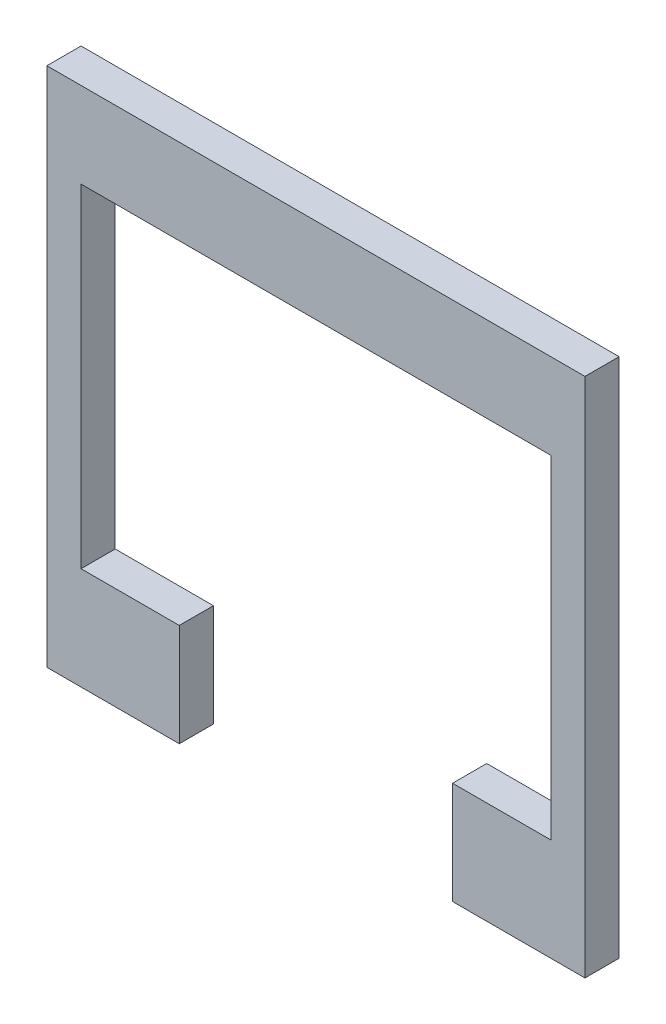
SolidWorks part; units mm, degrees
ref_plane "Front" through (0, 0, 0) normal (0, 0, 1) x (1, 0, 0)
ref_plane "Top" through (0, 0, 0) normal (0, 1, 0) x (1, 0, 0)
ref_plane "Right" through (0, 0, 0) normal (1, 0, 0) x (0, 0, -1)
sketch "Croquis1" plane through (0, 0, 0) normal (0, 0, 1) x (1, 0, 0)
  line L0 (0, 6.25) -> (0, -6.25) construction
  line L1 (-12.5, -6.25) -> (12.5, -6.25)
  line L2 (-12.5, -6.25) -> (-12.5, 6.25)
  line L3 (-12.5, 6.25) -> (12.5, 6.25)
  line L4 (12.5, -6.25) -> (12.5, 6.25)
  line L5 (-12.5, -6.25) -> (12.5, 6.25) construction
  line L6 (-12.5, 6.25) -> (12.5, -6.25) construction
  line L8 (-13.75, -11.25) -> (13.75, -11.25) construction
  line L9 (-13.75, -11.25) -> (-13.75, 8.25)
  line L10 (-13.75, 8.25) -> (13.75, 8.25)
  line L11 (13.75, -11.25) -> (13.75, 8.25)
  line L12 (-13.75, -11.25) -> (13.75, 8.25) construction
  line L13 (-13.75, 8.25) -> (13.75, -11.25) construction
  line L14 (-6, -16.25) -> (6, -16.25) construction
  line L15 (-6, -16.25) -> (-6, -6.25) construction
  line L16 (-6, -6.25) -> (6, -6.25) construction
  line L17 (6, -16.25) -> (6, -6.25) construction
  line L18 (-6, -16.25) -> (6, -6.25) construction
  line L19 (-6, -6.25) -> (6, -16.25) construction
  line L20 (-14.75, 12.25) -> (14.75, 12.25) construction
  line L21 (-14.75, 12.25) -> (-14.75, -16.25) construction
  line L22 (-14.75, -16.25) -> (14.75, -16.25) construction
  line L23 (14.75, 12.25) -> (14.75, -16.25) construction
  line L24 (-14.75, 12.25) -> (14.75, -16.25) construction
  line L25 (-14.75, -16.25) -> (14.75, 12.25) construction
  point P0 (0, 0)
  point P8 (0, 0)
  point P13 (0, -1.5)
  point P14 (0, -11.25)
  point P19 (0, -2)
  dimension "D1" = 12.5
  dimension "D2" = 25
  dimension "D3" = 2
  dimension "D4" = 27.5
  dimension "D5" = 19.5
  dimension "D6" = 12
  dimension "D7" = 5
  dimension "D8" = 1
  dimension "D9" = 4
sketch "Croquis4" plane through (0, 0, 0) normal (0, 0, 1) x (1, 0, 0)
  line L0 (-13.75, -11.25) -> (13.75, 8.25) construction
  line L1 (-13.75, -11.25) -> (-8, -11.25)
  line L2 (-13.75, -11.25) -> (-13.75, 8.25)
  line L3 (-13.75, 8.25) -> (13.75, 8.25)
  line L4 (13.75, -11.25) -> (13.75, 8.25)
  line L5 (-13.75, -11.25) -> (13.75, 8.25) construction
  line L6 (-13.75, 8.25) -> (13.75, -11.25) construction
  line L7 (0, 6.25) -> (0, -6.25) construction
  line L8 (-15.75, 13.25) -> (15.75, 13.25)
  line L9 (-15.75, 13.25) -> (-15.75, -17.25)
  line L10 (-15.75, -17.25) -> (-8, -17.25)
  line L11 (15.75, 13.25) -> (15.75, -17.25)
  line L12 (-15.75, 13.25) -> (15.75, -17.25) construction
  line L13 (-15.75, -17.25) -> (15.75, 13.25) construction
  line L14 (-14.75, 12.25) -> (14.75, 12.25) construction
  line L15 (-14.75, -16.25) -> (14.75, -16.25) construction
  line L16 (14.75, 12.25) -> (14.75, -16.25) construction
  line L17 (-8, -11.25) -> (-8, -17.25)
  line L18 (8, -11.25) -> (8, -17.25)
  line L19 (-6, -16.25) -> (-6, -6.25) construction
  line L20 (6, -16.25) -> (6, -6.25) construction
  line L21 (8, -17.25) -> (15.75, -17.25)
  line L22 (8, -11.25) -> (13.75, -11.25)
  point P0 (0, -1.5)
  point P8 (0, -2)
  dimension "D1" = 1
  dimension "D2" = 1
  dimension "D3" = 1
  dimension "D4" = 2
  dimension "D5" = 2
extrude "Saliente-Extruir1" add sketch "Croquis4" along normal blind 2
